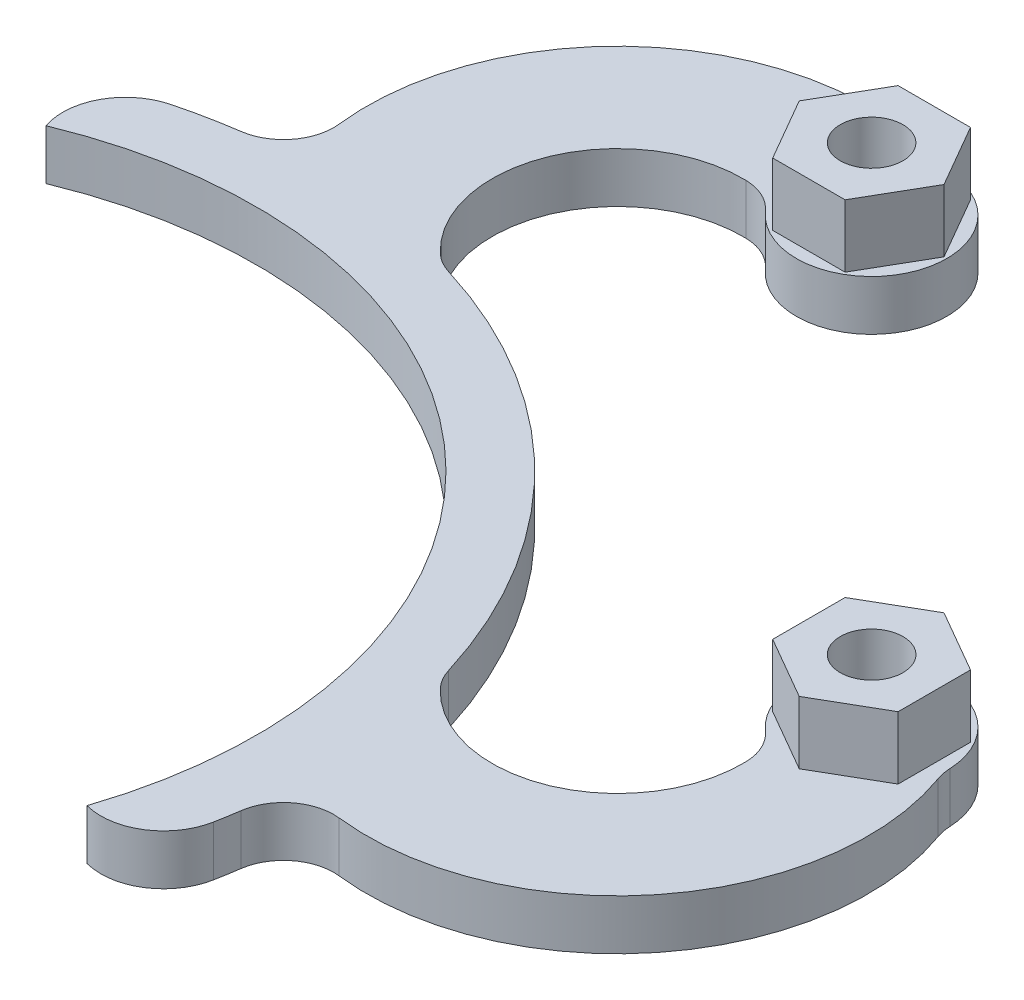
SolidWorks part; units mm, degrees
material "Plain Carbon Steel"
ref_plane "Front Plane" through (0, 0, 0) normal (0, 0, 1) x (1, 0, 0)
ref_plane "Top Plane" through (0, 0, 0) normal (0, 1, 0) x (1, 0, 0)
ref_plane "Right Plane" through (0, 0, 0) normal (1, 0, 0) x (0, 0, -1)
sketch "Sketch1" plane through (0, 0, 0) normal (0, 1, 0) x (1, 0, 0)
  line L0 (-8.771, -52.2468) -> (-4.9364, -61.4824) construction
  line L1 (0, 0) -> (-60.4576, -60.4576) construction
  line L2 (-35.3553, 0) -> (0, -35.3553) construction
  line L3 (-16.946, -47.1539) -> (-6.6076, -42.8614) construction
  line L4 (0, -35.3553) -> (-60.4576, -60.4576) construction
  line L5 (-0.1518, -0.1518) -> (-16.3442, -0.1518) construction
  line L6 (-34.6482, -34.6482) -> (-28.2603, -28.2603) construction
  line L7 (-61.9666, -18.9851) -> (-61.7848, -23.9818) construction
  line L8 (-89.8026, -31.1127) -> (-47.3967, 11.2932) construction
  arc A0 (-35.0965, 5.9944) -> (-39.8589, -3.9645) centre (-35.3553, 0) cw
  circle A3 centre (0, -35.3553) radius 2.5
  circle A4 centre (-35.3553, 0) radius 2.5
  arc A9 (5.9944, -35.0965) -> (-3.9645, -39.8589) centre (0, -35.3553) ccw
  arc A17 (-66.2853, -19.3689) -> (-19.3689, -66.2853) centre (-60.4576, -60.4576) ccw
  circle A18 centre (-60.4576, -60.4576) radius 36.5
  arc A19 (-48.3235, -20.7712) -> (-20.7712, -48.3235) centre (-60.4576, -60.4576) cw
  arc A20 (-2.6088, -42.7614) -> (-3.9645, -39.8589) centre (-6.6076, -42.8614) ccw
  arc A21 (-20.7712, -48.3235) -> (-19.8396, -49.9157) centre (-16.946, -47.1539) ccw
  arc A23 (-42.7614, -2.6088) -> (-39.8589, -3.9645) centre (-42.8614, -6.6076) cw
  arc A24 (-48.3235, -20.7712) -> (-49.9157, -19.8396) centre (-47.1539, -16.946) cw
  arc A27 (-14.9414, -62.8744) -> (6.2246, -36.2719) centre (-12.6057, -43.0113) ccw
  arc A28 (-19.8396, -49.9157) -> (-2.6088, -42.7614) centre (-12.6057, -43.0113) ccw
  arc A29 (6.2246, -36.2719) -> (5.9944, -35.0965) centre (9.9907, -34.924) cw
  arc A30 (-19.3689, -66.2853) -> (-14.9414, -62.8744) centre (-15.4085, -66.847) cw
  arc A31 (-62.8744, -14.9414) -> (-36.2719, 6.2246) centre (-43.0113, -12.6057) cw
  arc A32 (-66.2853, -19.3689) -> (-62.8744, -14.9414) centre (-66.847, -15.4085) ccw
  arc A33 (-49.9157, -19.8396) -> (-42.7614, -2.6088) centre (-43.0113, -12.6057) cw
  arc A34 (-36.2719, 6.2246) -> (-35.0965, 5.9944) centre (-34.924, 9.9907) ccw
  point P30 (-17.6777, -17.6777)
  point P33 (0, 0)
  point P55 (2.3406, -30.9115)
  point P58 (-18.9851, -61.9666)
  point P77 (0, 0)
  dimension "D2" = 6
  dimension "D3" = 5
  dimension "D4" = 50
  dimension "D5" = 10
  dimension "D7" = 20
  dimension "D8" = 73
  dimension "D6" = 4
  dimension "D13" = 4
  dimension "D14" = 60.5
  dimension "D10" = 45
  dimension "D11" = 5
extrude "Boss-Extrude1" add sketch "Sketch1" along normal blind 4
sketch "Sketch2" plane through (0, 4, 0) normal (0, 1, 0) x (1, 0, 0)
  line L0 (0, 0) -> (-42.2858, -42.2858) construction
  line L1 (-32.4686, -5) -> (-29.5818, 0)
  line L2 (-29.5818, 0) -> (-32.4686, 5)
  line L3 (-32.4686, 5) -> (-38.2421, 5)
  line L4 (-38.2421, 5) -> (-41.1288, 0)
  line L5 (-41.1288, 0) -> (-38.2421, -5)
  line L6 (-38.2421, -5) -> (-32.4686, -5)
  line L7 (-5, -38.2421) -> (-5, -32.4686)
  line L8 (0, -41.1288) -> (-5, -38.2421)
  line L9 (5, -38.2421) -> (0, -41.1288)
  line L10 (5, -32.4686) -> (5, -38.2421)
  line L11 (0, -29.5818) -> (5, -32.4686)
  line L12 (-5, -32.4686) -> (0, -29.5818)
  circle A0 centre (-35.3553, 0) radius 5 construction
  circle A1 centre (-35.3553, 0) radius 2.5 construction
  circle A2 centre (-35.3553, 0) radius 2.5
  circle A3 centre (0, -35.3553) radius 5 construction
  circle A4 centre (0, -35.3553) radius 2.5
  circle A5 centre (0, -35.3553) radius 2.5 construction
  dimension "D1" = 10
extrude "Boss-Extrude2" add sketch "Sketch2" along normal blind 5
sketch "Sketch3" plane through (0, 4, 0) normal (0, 1, 0) x (1, 0, 0)
  circle A0 centre (-87.7903, -89.7621) radius 64.4112
extrude "Cut-Extrude1" cut sketch "Sketch3" against normal blind 10
fillet "Fillet1" radius 5 2 edges at (-82.8827, 2, 25.5382) (-24.0632, 2, 80.3999)
